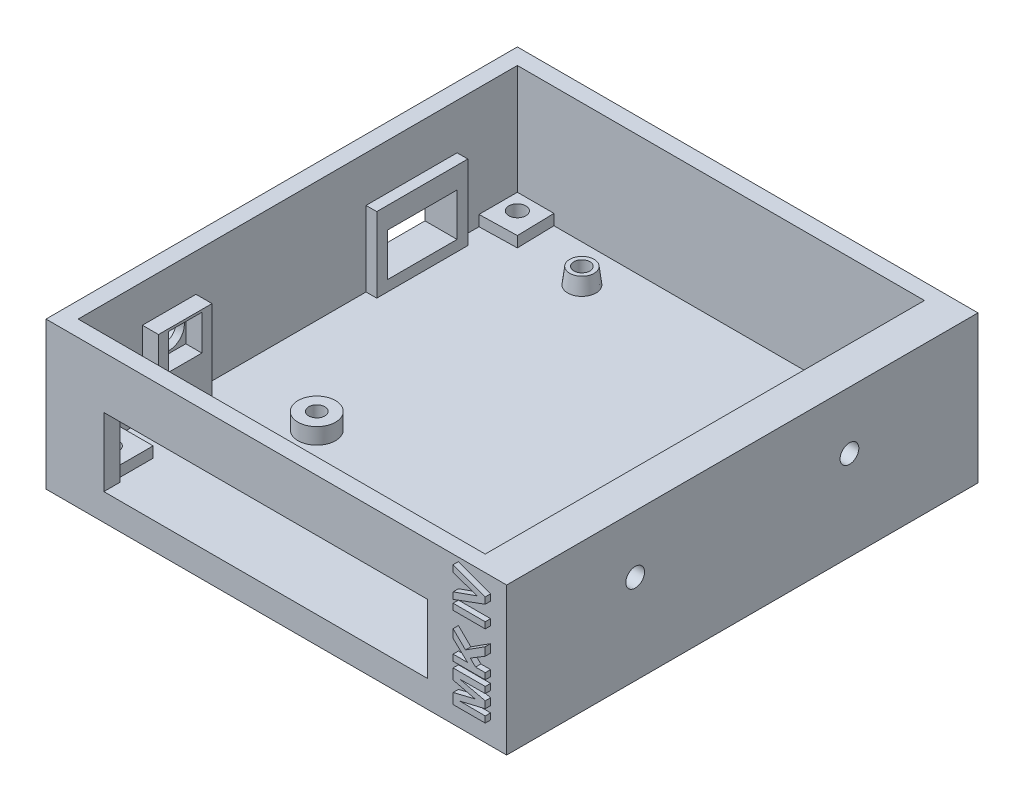
SolidWorks part; units mm, degrees
ref_plane "Спереди" through (0, 0, 0) normal (0, 0, 1) x (1, 0, 0)
ref_plane "Сверху" through (0, 0, 0) normal (0, 1, 0) x (1, 0, 0)
ref_plane "Справа" through (0, 0, 0) normal (1, 0, 0) x (0, 0, -1)
sketch "Sketch1" plane through (0, 0, 0) normal (0, 1, 0) x (1, 0, 0)
  line L1 (41, 44) -> (-41, 44)
  line L2 (41, 44) -> (41, -44)
  line L3 (41, -44) -> (-41, -44)
  line L4 (-41, 44) -> (-41, -44)
  line L5 (41, 44) -> (-41, -44) construction
  line L6 (41, -44) -> (-41, 44) construction
  point P0 (0, 0)
  dimension "D1" = 82
  dimension "D2" = 88
extrude "Boss-Extrude1" add sketch "Sketch1" along normal blind 5
sketch "Sketch2" plane through (0, 5, 0) normal (0, 1, 0) x (1, 0, 0)
  line L1 (-41, 44) -> (41, 44)
  line L2 (-41, 44) -> (-41, -44)
  line L3 (-41, -44) -> (41, -44)
  line L4 (41, 44) -> (41, -44)
  line L5 (-41, 44) -> (41, -44) construction
  line L6 (-41, -44) -> (41, 44) construction
  line L7 (-38, 41) -> (38, 41)
  line L8 (-38, 41) -> (-38, -41)
  line L9 (-38, -41) -> (38, -41)
  line L10 (38, 41) -> (38, -41)
  line L11 (-38, 41) -> (38, -41) construction
  line L12 (-38, -41) -> (38, 41) construction
  point P0 (0, 0)
  point P7 (0, 0)
  dimension "D1" = 3
  dimension "D2" = 3
  dimension "D3" = 76
  dimension "D4" = 82
  dimension "D5" = 82
  dimension "D6" = 88
extrude "Boss-Extrude2" add sketch "Sketch2" along normal blind 22.5
sketch "Эскиз1" plane through (0, 5, 0) normal (0, 1, 0) x (1, 0, 0)
  line L0 (-34.3, 36.65) -> (34.3, 36.65) construction
  line L1 (34.3, -16.65) -> (-34.3, 36.65) construction
  line L2 (-34.3, -16.65) -> (34.3, 36.65) construction
  line L3 (0, 41) -> (0, -41) construction
  line L4 (-38, -41) -> (38, -41) construction
  line L5 (31.8, -14.15) -> (-34.3, -14.15) construction
  line L6 (38, 41) -> (-38, 41) construction
  line L7 (34.3, 36.65) -> (34.3, -16.65) construction
  line L8 (34.3, -16.65) -> (-34.3, -16.65) construction
  line L9 (-34.3, -16.65) -> (-34.3, 36.65) construction
  line L10 (-34.3, 36.65) -> (-20.3, 36.65) construction
  line L11 (31.8, 36.65) -> (31.8, 18.85) construction
  line L12 (31.8, 18.85) -> (31.8, 34.05) construction
  line L13 (-20.3, 36.65) -> (-19, 36.65) construction
  line L14 (-20.3, 36.65) -> (-20.3, -16.65) construction
  line L15 (-19, 36.65) -> (31.8, 36.65) construction
  line L16 (31.8, 36.65) -> (31.8, -16.65) construction
  line L17 (31.8, -16.65) -> (31.8, -14.15) construction
  line L18 (31.8, 34.05) -> (-19, 34.05) construction
  line L19 (-19, 36.65) -> (-19, -16.65) construction
  circle A0 centre (31.8, -9.05) radius 1.5
  circle A1 centre (-20.3, -14.15) radius 1.5
  circle A2 centre (31.8, 18.85) radius 1.5
  circle A3 centre (-19, 34.05) radius 1.5
  circle A4 centre (-20.3, -14.15) radius 3.5
  circle A5 centre (-19, 34.05) radius 3.5
  circle A6 centre (31.8, 18.85) radius 3.5
  circle A7 centre (31.8, -9.05) radius 3.5
  point P3 (0, 10)
  point P11 (-20.3, -14.15)
  point P34 (0, 0)
  dimension "D12" = 3
  dimension "D2" = 7
  dimension "D3" = 53.3
  dimension "D4" = 68.6
  dimension "D5" = 14
  dimension "D6" = 1.3
  dimension "D7" = 50.8
  dimension "D8" = 2.5
  dimension "D9" = 5.1
  dimension "D10" = 27.9
  dimension "D11" = 15.2
  dimension "D13" = 31
extrude "Boss-Extrude3" add sketch "Эскиз1" along normal blind 3
sketch "Sketch4" plane through (-41, 0, 0) normal (-1, 0, 0) x (0, 0, 1)
  line L0 (0, 27.5) -> (0, 0) construction
  line L1 (-27.75, 17) -> (-14.75, 17)
  line L2 (-27.75, 27.5) -> (-27.75, 5) construction
  line L3 (-44, 0) -> (44, 0) construction
  line L4 (-14.75, 5) -> (-14.75, 27.5) construction
  line L5 (26.75, 5) -> (-26.75, 5) construction
  line L6 (-44, 27.5) -> (44, 27.5) construction
  line L7 (-27.75, 17) -> (-27.75, 5)
  line L8 (-27.75, 5) -> (-14.75, 5)
  line L9 (-41, 5) -> (41, 5) construction
  line L10 (-14.75, 5) -> (-14.75, 17)
  line L11 (-44, 27.5) -> (-44, 0) construction
  point P7 (0, 5)
  point P8 (-21.25, 5)
  dimension "D1" = 53.5
  dimension "D2" = 16.25
  dimension "D3" = 13
  dimension "D4" = 12
extrude "Cut-Extrude1" cut sketch "Sketch4" against normal up to surface (3 mm away) up to face at (-38, 16.25, 0)
sketch "Sketch7" plane through (0, 0, 0) normal (0, -1, 0) x (1, 0, 0)
  line L0 (-41, -44) -> (-41, 44) construction
  line L1 (-35, 38) -> (35, -38) construction
  line L2 (35, -38) -> (-35, -38) construction
  line L3 (-35, -38) -> (-35, 38) construction
  line L4 (-35, 38) -> (35, 38) construction
  line L5 (35, 38) -> (35, -38) construction
  line L6 (-41, 44) -> (41, 44) construction
  line L8 (41, 44) -> (41, -44) construction
  line L9 (41, -44) -> (-41, -44) construction
  circle A0 centre (35, -38) radius 1.6
  circle A1 centre (-35, -38) radius 1.6
  circle A2 centre (-35, 38) radius 1.6
  circle A3 centre (35, 38) radius 1.6
  dimension "D2" = 3.2
  dimension "D3" = 6
  dimension "D1" = 6
  dimension "D4" = 6
  dimension "D5" = 6
extrude "Cut-Extrude3" cut sketch "Sketch7" against normal through all
sketch "Sketch8" plane through (0, 0, 0) normal (0, -1, 0) x (1, 0, 0)
  line L0 (-41, 44) -> (41, 44) construction
  line L1 (33.375, 35.1854) -> (36.625, 35.1854)
  line L2 (36.625, 35.1854) -> (38.25, 38)
  line L3 (38.25, 38) -> (36.625, 40.8146)
  line L4 (36.625, 40.8146) -> (33.375, 40.8146)
  line L5 (33.375, 40.8146) -> (31.75, 38)
  line L6 (31.75, 38) -> (33.375, 35.1854)
  line L7 (33.375, -35.1854) -> (31.75, -38)
  line L8 (31.75, -38) -> (33.375, -40.8146)
  line L9 (33.375, -40.8146) -> (36.625, -40.8146)
  line L10 (36.625, -40.8146) -> (38.25, -38)
  line L11 (38.25, -38) -> (36.625, -35.1854)
  line L12 (36.625, -35.1854) -> (33.375, -35.1854)
  line L13 (-36.625, -35.1854) -> (-38.25, -38)
  line L14 (-38.25, -38) -> (-36.625, -40.8146)
  line L15 (-36.625, -40.8146) -> (-33.375, -40.8146)
  line L16 (-33.375, -40.8146) -> (-31.75, -38)
  line L17 (-31.75, -38) -> (-33.375, -35.1854)
  line L18 (-33.375, -35.1854) -> (-36.625, -35.1854)
  line L19 (-36.625, 35.1854) -> (-33.375, 35.1854)
  line L20 (-33.375, 35.1854) -> (-31.75, 38)
  line L21 (-31.75, 38) -> (-33.375, 40.8146)
  line L22 (-33.375, 40.8146) -> (-36.625, 40.8146)
  line L23 (-36.625, 40.8146) -> (-38.25, 38)
  line L24 (-38.25, 38) -> (-36.625, 35.1854)
  line L25 (41, -44) -> (-41, -44) construction
  circle A0 centre (35, 38) radius 3.25 construction
  circle A1 centre (35, -38) radius 3.25 construction
  circle A2 centre (-35, -38) radius 3.25 construction
  circle A3 centre (-35, 38) radius 3.25 construction
  dimension "D1" = 6.5
extrude "Cut-Extrude4" cut sketch "Sketch8" against normal blind 3.5
sketch "Sketch10" plane through (-38, 0, 0) normal (1, 0, 0) x (0, 0, -1)
  line L0 (27.75, 17) -> (14.75, 5) construction
  line L2 (14.75, 5) -> (27.75, 5)
  line L3 (14.75, 5) -> (14.75, 17)
  line L4 (14.75, 17) -> (27.75, 17)
  line L5 (27.75, 5) -> (27.75, 17)
  line L6 (14.75, 5) -> (27.75, 17) construction
  line L7 (14.75, 17) -> (27.75, 5) construction
  line L8 (12.75, 3) -> (29.75, 3)
  line L9 (12.75, 3) -> (12.75, 19)
  line L10 (12.75, 19) -> (29.75, 19)
  line L11 (29.75, 3) -> (29.75, 19)
  line L12 (12.75, 3) -> (29.75, 19) construction
  line L13 (12.75, 19) -> (29.75, 3) construction
  point P4 (21.25, 11)
  point P5 (21.25, 11)
  dimension "D1" = 2
  dimension "D2" = 2
extrude "Boss-Extrude6" add sketch "Sketch10" along normal blind 2
chamfer "Chamfer1" distance 10 angle 7 1 edges at (-19, 8, -30.55) first distance on face at (-19, 8, -30.55)
sketch "Sketch11" plane through (0, 5, 0) normal (0, 1, 0) x (1, 0, 0)
  circle A0 centre (-20.3, -14.15) radius 1.5
  circle A1 centre (-19, 34.05) radius 1.5
  circle A2 centre (31.8, -9.05) radius 1.5
  circle A3 centre (31.8, 18.85) radius 1.5
  circle A4 centre (31.8, 18.85) radius 1.5 construction
extrude "Cut-Extrude5" cut sketch "Sketch11" against normal through all
sketch "Sketch12" plane through (0, 0, 44) normal (0, 0, 1) x (1, 0, 0)
  line L0 (-41, 11.4) -> (41, 11.4) construction
  line L1 (-41, 27.5) -> (-41, 0) construction
  line L2 (41, 27.5) -> (41, 0) construction
  line L3 (-38, 5) -> (38, 5) construction
  line L4 (30.2, 17.8) -> (-30.2, 17.8)
  line L5 (30.2, 17.8) -> (30.2, 5)
  line L6 (30.2, 5) -> (-30.2, 5)
  line L7 (-30.2, 17.8) -> (-30.2, 5)
  line L8 (30.2, 17.8) -> (-30.2, 5) construction
  line L9 (30.2, 5) -> (-30.2, 17.8) construction
  point P6 (0, 11.4)
  dimension "D1" = 12.8
  dimension "D2" = 60.4
extrude "Cut-Extrude6" cut sketch "Sketch12" against normal up to surface (3 mm away) up to face at (0, 16.25, 41)
sketch "Sketch13" plane through (41, 0, 0) normal (1, 0, 0) x (0, 0, -1)
  line L0 (-44, 16.75) -> (44, 16.75) construction
  line L3 (-44, 27.5) -> (-44, 0) construction
  line L4 (44, 27.5) -> (44, 0) construction
  circle A0 centre (-20, 16.75) radius 1.75
  circle A1 centre (20, 16.75) radius 1.75
  point P10 (0, 16.75)
  point P11 (-44, 13.75)
  dimension "D1" = 40
  dimension "D4" = 3.5
  dimension "D2" = 20
  dimension "D3" = 3
extrude "Cut-Extrude7" cut sketch "Sketch13" against normal up to surface (3 mm away) up to face at (38, 16.25, 0)
sketch "Sketch14" plane through (41, 0, 0) normal (1, 0, 0) x (0, 0, -1)
  line L0 (-44, 13.75) -> (44, 13.75) construction
  line L1 (-44, 27.5) -> (-44, 0) construction
  line L2 (44, 27.5) -> (44, 0) construction
  line L4 (44, 0) -> (-44, 0)
  line L5 (44, 0) -> (44, 27.5)
  line L6 (44, 27.5) -> (-44, 27.5)
  line L7 (-44, 0) -> (-44, 27.5)
  line L8 (44, 0) -> (-44, 27.5) construction
  line L9 (44, 27.5) -> (-44, 0) construction
  circle A0 centre (-20, 16.75) radius 1.75
  circle A1 centre (20, 16.75) radius 1.75
  circle A2 centre (20, 16.75) radius 1.75 construction
  point P6 (0, 13.75)
extrude "Boss-Extrude7" add sketch "Sketch14" along normal blind 4
sketch "Sketch15" plane through (38, 0, 0) normal (-1, 0, 0) x (0, 0, 1)
  circle A0 centre (20, 16.75) radius 3.75
  circle A1 centre (-20, 16.75) radius 3.75
  dimension "D1" = 7.5
extrude "Cut-Extrude8" cut sketch "Sketch15" against normal blind 3
sketch "Sketch16" plane through (-41, 0, 0) normal (-1, 0, 0) x (0, 0, 1)
  line L0 (44, 16.75) -> (-44, 16.75) construction
  line L1 (44, 27.5) -> (44, 0) construction
  line L2 (-44, 27.5) -> (-44, 0) construction
  circle A0 centre (24, 16.75) radius 2.25
  point P6 (44, 13.75)
  dimension "D2" = 4.5
  dimension "D1" = 3
  dimension "D3" = 20
extrude "Cut-Extrude9" cut sketch "Sketch16" against normal up to next
sketch "Sketch17" plane through (-38, 0, 0) normal (1, 0, 0) x (0, 0, -1)
  line L0 (-29, 20.5) -> (-29, 5)
  line L1 (-20.9, 13.45) -> (-27.1, 13.45)
  line L2 (-20.9, 13.45) -> (-20.9, 20.05)
  line L3 (-20.9, 20.05) -> (-27.1, 20.05)
  line L4 (-27.1, 13.45) -> (-27.1, 20.05)
  line L5 (-20.9, 13.45) -> (-27.1, 20.05) construction
  line L6 (-20.9, 20.05) -> (-27.1, 13.45) construction
  line L7 (12.75, 5) -> (-41, 5) construction
  line L8 (-29, 5) -> (-19, 5)
  line L9 (-19, 20.5) -> (-29, 20.5)
  line L10 (-19, 5) -> (-19, 20.5)
  line L11 (-17.8, 12.1) -> (-29, 20.5) construction
  line L12 (-19, 20.5) -> (-29, 13) construction
  point P0 (-24, 16.75)
  point P6 (-24, 16.75)
  dimension "D1" = 6.2
  dimension "D3" = 10
extrude "Boss-Extrude8" add sketch "Sketch17" along normal blind 3
chamfer "Chamfer2" distance 1 angle 30 1 edges at (-38, 16.75, 21.75) first distance on face at (-38, 16.75, 21.75)
sketch "Sketch20" plane through (-41, 0, 0) normal (-1, 0, 0) x (0, 0, 1)
  circle A0 centre (24, 16.75) radius 3
  circle A1 centre (24, 16.75) radius 5
  dimension "D1" = 6
  dimension "D2" = 10
extrude "Boss-Extrude10" add sketch "Sketch20" along normal blind 1
fillet "Fillet3" radius 2 1 edges at (-41, 16.75, 19)
sketch "Sketch21" plane through (0, 5, 0) normal (0, 1, 0) x (1, 0, 0)
  line L0 (-41, 27.75) -> (-36, 27.75)
  line L1 (-36, 27.75) -> (-36, 14.75)
  line L2 (-36, 14.75) -> (-41, 14.75)
  line L3 (-41, 14.75) -> (-41, 27.75)
extrude "Boss-Extrude11" add sketch "Sketch21" along normal blind 2
sketch "Sketch22" plane through (0, 0, 44) normal (0, 0, 1) x (1, 0, 0)
  line L0 (42, 0) -> (42, 27.5) construction
  line L1 (-41, 0) -> (45, 0) construction
  line L2 (-41, 27.5) -> (45, 27.5) construction
  line L3 (45, 27.5) -> (45, 0) construction
  text T0 "<b> MK IV</b>" font "Arial" height 6
  dimension "D1" = 3
extrude "Boss-Extrude12" add sketch "Sketch22" along normal blind 1
sketch "Sketch27" plane through (0, 17, 0) normal (0, -1, 0) x (1, 0, 0)
  line L0 (-41, -27.75) -> (-41, -14.75)
  line L1 (-41, -14.75) -> (-36, -14.75)
  line L2 (-36, -14.75) -> (-36, -27.75)
  line L3 (-36, -27.75) -> (-41, -27.75)
extrude "Boss-Extrude17" add sketch "Sketch27" along normal blind 2
sketch "Sketch23" plane through (0, 5, 0) normal (0, 1, 0) x (1, 0, 0)
  line L2 (-31, -41) -> (-31, -34)
  line L3 (-38, -41) -> (-30.2, -41) construction
  line L4 (-38, -29) -> (-38, -41) construction
  line L5 (-38, -34) -> (-38, -41)
  line L6 (-31, -34) -> (-38, -34)
  line L7 (-31, -41) -> (-38, -41)
  line L8 (31, -41) -> (31, -34)
  line L9 (30.2, -41) -> (38, -41) construction
  line L10 (31, -34) -> (38, -34)
  line L11 (38, -41) -> (38, 41) construction
  line L12 (38, -34) -> (38, -41)
  line L13 (38, -41) -> (31, -41)
  line L14 (38, 34) -> (31, 34)
  line L15 (31, 34) -> (31, 41)
  line L16 (38, 41) -> (-38, 41) construction
  line L17 (31, 41) -> (38, 41)
  line L18 (38, 41) -> (38, 34)
  line L19 (-38, 41) -> (-38, 29.75) construction
  line L20 (-38, 33.8379) -> (-31.0019, 34.0019)
  line L21 (-31.0019, 34.0019) -> (-31.1659, 41)
  line L22 (-31.1659, 41) -> (-38, 41)
  line L23 (-38, 41) -> (-38, 33.8379)
  circle A4 centre (-35, -38) radius 1.6
  circle A5 centre (-35, 38) radius 1.6
  circle A6 centre (35, 38) radius 1.6
  circle A7 centre (35, -38) radius 1.6
  circle A8 centre (-35, -38) radius 1.6 construction
  dimension "D1" = 7
extrude "Boss-Extrude13" add sketch "Sketch23" along normal blind 2
sketch "Sketch25" plane through (-41, 0, 0) normal (-1, 0, 0) x (0, 0, 1)
  line L0 (-27.75, 11) -> (-14.75, 11) construction
  line L1 (-27.75, 15) -> (-27.75, 7) construction
  line L2 (-14.75, 7) -> (-14.75, 15) construction
  line L4 (-14.75, 7) -> (-27.75, 7)
  line L5 (-14.75, 7) -> (-14.75, 15)
  line L6 (-14.75, 15) -> (-27.75, 15)
  line L7 (-27.75, 7) -> (-27.75, 15)
  line L8 (-14.75, 7) -> (-27.75, 15) construction
  line L9 (-14.75, 15) -> (-27.75, 7) construction
  line L10 (-12.75, 5) -> (-29.75, 5)
  line L11 (-12.75, 5) -> (-12.75, 17)
  line L12 (-12.75, 17) -> (-29.75, 17)
  line L13 (-29.75, 5) -> (-29.75, 17)
  line L14 (-12.75, 5) -> (-29.75, 17) construction
  line L15 (-12.75, 17) -> (-29.75, 5) construction
  point P6 (-21.25, 11)
  point P12 (-21.25, 11)
  point P17 (0, 0)
  point P18 (0, 0)
  dimension "D1" = 2
  dimension "D2" = 2
extrude "Boss-Extrude15" add sketch "Sketch25" along normal up to surface (1 mm away) up to face at (-42, 16.75, 29)
fillet "Fillet4" radius 2 4 edges at (-41, 17, -21.25) (-41, 11, -29.75) (-41, 5, -21.25) (-41, 11, -12.75)
